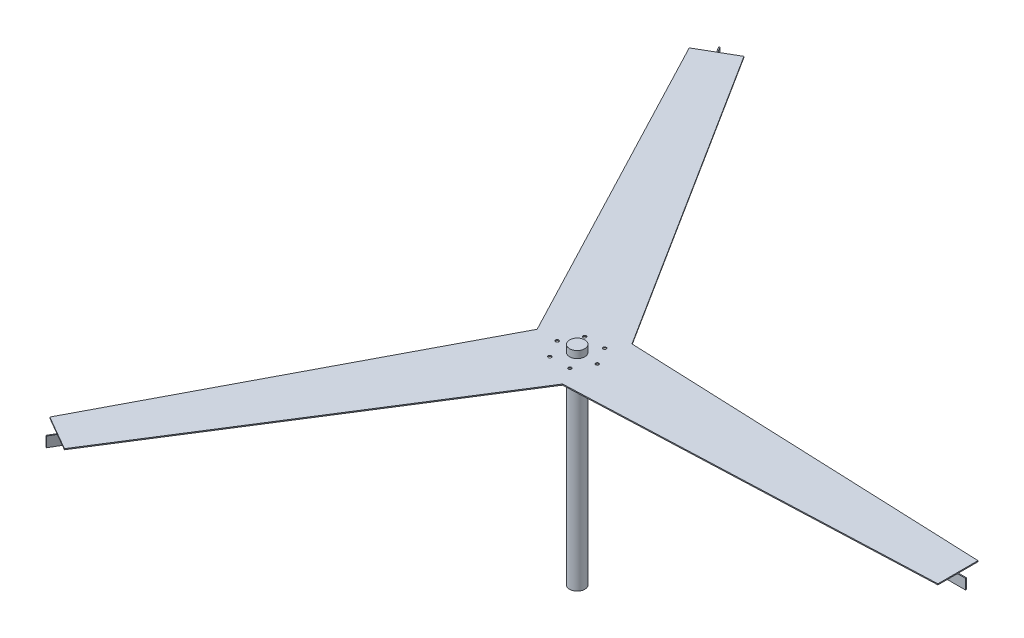
SolidWorks part; units mm, degrees
ref_plane "Alzado" through (0, 0, 0) normal (0, 0, 1) x (1, 0, 0)
ref_plane "Planta" through (0, 0, 0) normal (0, 1, 0) x (1, 0, 0)
ref_plane "Vista lateral" through (0, 0, 0) normal (1, 0, 0) x (0, 0, -1)
sketch "Croquis1" plane through (0, 0, 0) normal (0, 1, 0) x (1, 0, 0)
  line L0 (0, 0) -> (950, 0) construction
  line L1 (-431.6987, -847.7241) -> (-518.3013, -797.7241)
  line L2 (-100, 0) -> (-518.3013, -797.7241)
  line L3 (-431.6987, -847.7241) -> (50, -86.6025)
  line L6 (950, 50) -> (950, -50)
  line L9 (50, 86.6025) -> (0, 0) construction
  line L10 (0, 0) -> (-475, -822.7241) construction
  line L18 (0, 0) -> (50, -86.6025) construction
  line L19 (50, -86.6025) -> (0, 0) construction
  line L20 (0, 0) -> (9.525, 16.4978) construction
  line L22 (50, -86.6025) -> (950, -50)
  line L25 (950, 50) -> (50, 86.6025)
  line L27 (0, 0) -> (-100, 0) construction
  line L28 (-518.3013, 797.7241) -> (-431.6987, 847.7241)
  line L29 (50, 86.6025) -> (-431.6987, 847.7241)
  line L30 (-518.3013, 797.7241) -> (-100, 0)
  line L31 (0, 0) -> (-475, 822.7241) construction
  line L32 (-100, 0) -> (0, 0) construction
  line L33 (0, 0) -> (50, 86.6025) construction
  line L34 (50, 86.6025) -> (50, -86.6025) construction
  circle A0 centre (0, 0) radius 19.05
  point P3 (475, 0)
  point P8 (-237.5, -411.3621)
  point P17 (-237.5, 411.3621)
  point P23 (0, 0)
  point P26 (0, 0)
  dimension "D2" = 38.1
  dimension "D3" = 3
  dimension "D4" = 950
  dimension "D6" = 100
  dimension "D9" = 60
  dimension "D12" = 100
extrude "Saliente-Extruir3" add sketch "Croquis1" along normal blind 2.5 contours L25 L28 L22 L6 A0 region at (-463.7857, 0, 803.3003)
sketch "Croquis2" plane through (0, 0, 0) normal (0, -1, 0) x (1, 0, 0)
  line L0 (950, 0) -> (65, 0) construction
  line L1 (950, -50) -> (950, 50) construction
  line L2 (65, 1.25) -> (65, -1.25)
  line L3 (65, -1.25) -> (950, -1.25)
  line L4 (950, -1.25) -> (950, 1.25)
  line L5 (950, 1.25) -> (65, 1.25)
  line L18 (-473.9175, -823.3491) -> (-31.4175, -56.9167)
  line L22 (-33.5825, -55.6667) -> (-476.0825, -822.0991)
  line L23 (-476.0825, -822.0991) -> (-473.9175, -823.3491)
  line L24 (-475, -822.7241) -> (-32.5, -56.2917) construction
  line L25 (-31.4175, -56.9167) -> (-33.5825, -55.6667)
  line L26 (-476.0825, 822.0991) -> (-33.5825, 55.6667)
  line L27 (-31.4175, 56.9167) -> (-473.9175, 823.3491)
  line L28 (-473.9175, 823.3491) -> (-476.0825, 822.0991)
  line L29 (-475, 822.7241) -> (-32.5, 56.2917) construction
  line L30 (-33.5825, 55.6667) -> (-31.4175, 56.9167)
  point P8 (65, 0)
  point P21 (5, 2.8868)
  point P26 (0, 0)
  dimension "D1" = 885
  dimension "D2" = 2.5
  dimension "D3" = 3
extrude "Saliente-Extruir4" add sketch "Croquis2" along normal blind 25.4
sketch "Croquis4" plane through (0, 2.5, 0) normal (0, 1, 0) x (1, 0, 0)
  line L0 (0, 0) -> (50, 0) construction
  line L1 (50, 0) -> (25, 43.3013) construction
  line L2 (25, 43.3013) -> (-25, 43.3013) construction
  line L3 (-25, 43.3013) -> (-50, 0) construction
  line L4 (-50, 0) -> (-25, -43.3013) construction
  line L5 (-25, -43.3013) -> (25, -43.3013) construction
  line L6 (25, -43.3013) -> (50, 0) construction
  circle A2 centre (0, 0) radius 43.3013 construction
  circle A3 centre (25, -43.3013) radius 4
  circle A4 centre (-25, -43.3013) radius 4
  circle A5 centre (-50, 0) radius 4
  circle A6 centre (-25, 43.3013) radius 4
  circle A7 centre (25, 43.3013) radius 4
  circle A8 centre (50, 0) radius 4
  point P26 (0, 0)
  dimension "D4" = 8
  dimension "D5" = 50
  dimension "D6" = 86.6025
  dimension "D2" = 50
  dimension "D7" = 50
  dimension "D8" = 6
extrude "Cortar-Extruir1" cut sketch "Croquis4" against normal blind 2.54
sketch "Croquis5" plane through (0, 0, 0) normal (0, -1, 0) x (1, 0, 0)
  circle A0 centre (0, 0) radius 19.05
extrude "Saliente-Extruir5" add sketch "Croquis5" along normal blind 500 and the other way blind 20 separate body
sketch "Croquis6" plane through (950, 0, 0) normal (1, 0, 0) x (0, 0, -1)
  line L1 (-1.25, -25.4) -> (1.25, -25.4)
  line L2 (-1.25, -25.4) -> (-1.25, 0)
  line L3 (-1.25, 0) -> (1.25, 0)
  line L4 (1.25, -25.4) -> (1.25, 0)
extrude "Saliente-Extruir6" add sketch "Croquis6" along normal blind 20
pattern_circular "MatrizC1" count 3 every 120 about axis through (0, 20, 0) along (0, -1, 0) of "Saliente-Extruir6"
